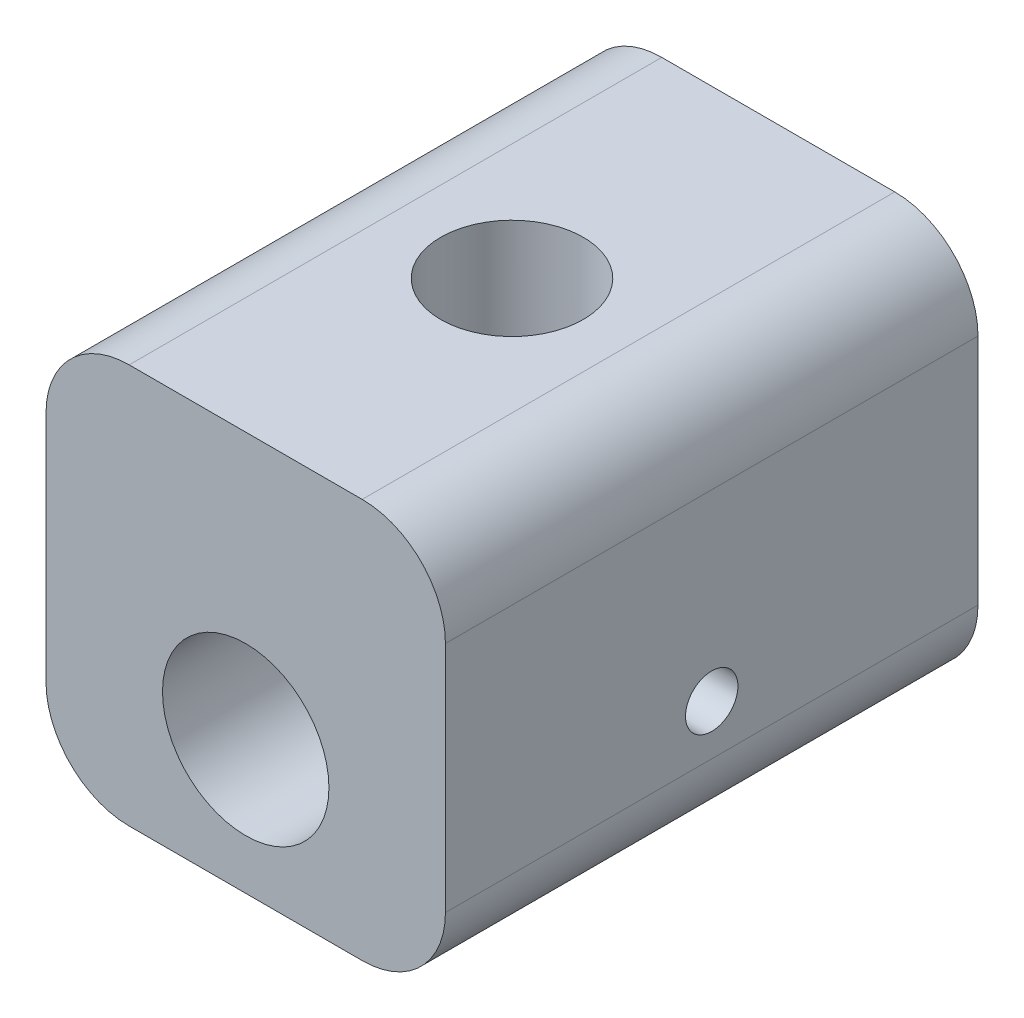
SolidWorks part; units mm, degrees
ref_plane "Front Plane" through (0, 0, 0) normal (0, 0, 1) x (1, 0, 0)
ref_plane "Top Plane" through (0, 0, 0) normal (0, 1, 0) x (1, 0, 0)
ref_plane "Right Plane" through (0, 0, 0) normal (1, 0, 0) x (0, 0, -1)
sketch "Sketch1" plane through (0, 0, 0) normal (0, 0, 1) x (1, 0, 0)
  line L0 (0, -6.35) -> (0, 12.7) construction
  line L5 (-9.525, 12.7) -> (9.525, 12.7)
  line L6 (-9.525, 12.7) -> (-9.525, -6.35)
  line L7 (-9.525, -6.35) -> (9.525, -6.35)
  line L8 (9.525, 12.7) -> (9.525, -6.35)
  circle A0 centre (0, 0) radius 3.9688
  point P9 (0, 0)
  dimension "D1" = 7.9375
  dimension "D2" = 19.05
  dimension "D3" = 6.35
  dimension "D4" = 12.7
extrude "Boss-Extrude1" add sketch "Sketch1" along normal blind 25.4
fillet "Fillet1" radius 3.9688 4 edges at (9.525, -6.35, 12.7) (-9.525, -6.35, 12.7) (-9.525, 12.7, 12.7) (9.525, 12.7, 12.7)
hole_wizard "Tap Drill for M8x1.25 Tap1" positions "Sketch2" profile "Sketch4" hole size "M8x1.25" standard "ANSI Metric" end condition up to next
sketch "Sketch2" plane through (0, 12.7, 0) normal (0, 1, 0) x (1, 0, 0)
  point P0 (0, -12.7)
sketch "Sketch4" plane through (0, 12.7, 12.7) normal (1, 0, 0) x (0, 0, 1)
  line L0 (0, 0) -> (0, 8.7312)
  line L1 (0, 8.7312) -> (3.4, 8.7312)
  line L2 (3.4, 8.7312) -> (3.4, 0)
  line L5 (3.4, 0) -> (0, 0)
  line L11 (0, -6.35) -> (0, 107.95) construction
  dimension "Thru Hole Dia." = 6.8
  dimension "Thru Hole Depth" = 8.7312
hole_wizard "Tap Drill for M3x0.5 Tap1" positions "Sketch5" profile "Sketch6" hole size "M3x0.5" standard "ANSI Metric" end condition up to next
sketch "Sketch5" plane through (9.525, 0, 0) normal (1, 0, 0) x (0, 0, -1)
  point P0 (-12.7, 0)
sketch "Sketch6" plane through (9.525, 0, 12.7) normal (0, 1, 0) x (0, 0, -1)
  line L0 (0, 0) -> (0, 5.5562)
  line L1 (0, 5.5562) -> (1.25, 5.5562)
  line L2 (1.25, 5.5562) -> (1.25, 0)
  line L5 (1.25, 0) -> (0, 0)
  line L11 (0, -6.35) -> (0, 107.95) construction
  dimension "Thru Hole Dia." = 2.5
  dimension "Thru Hole Depth" = 5.5562
